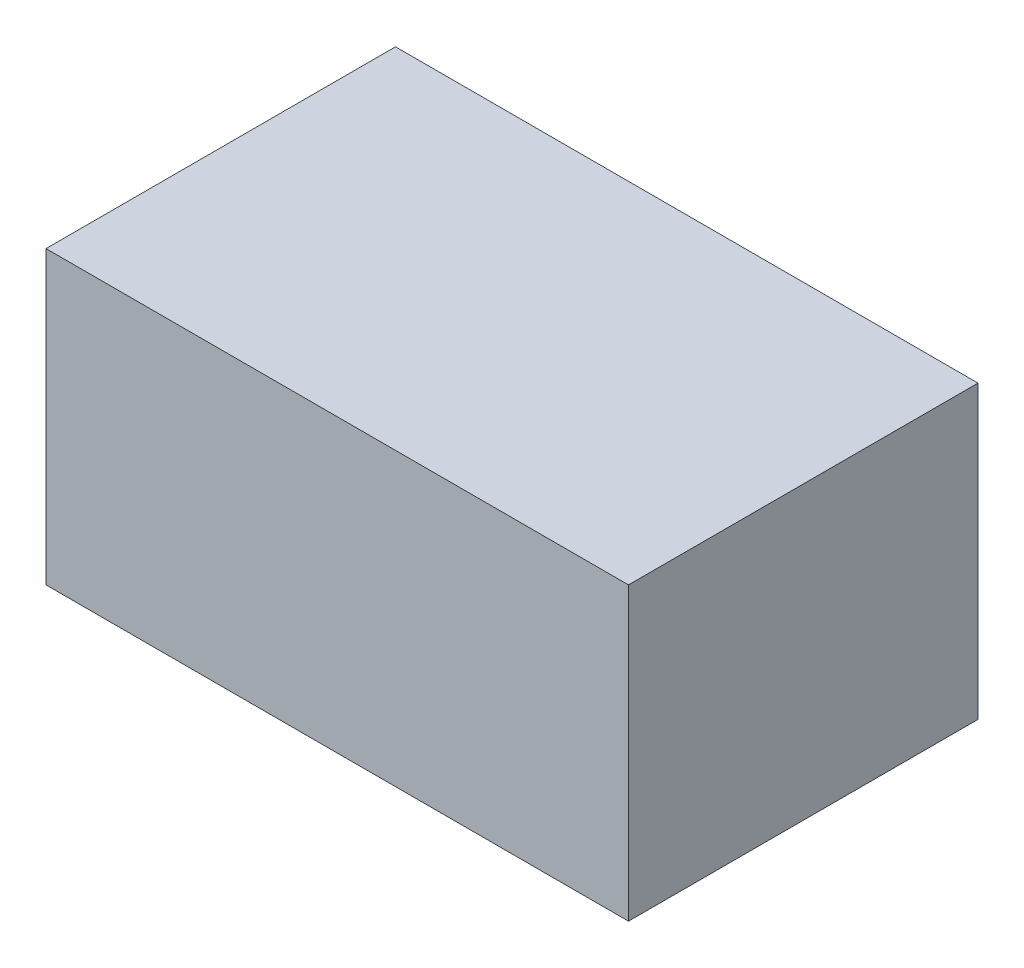
SolidWorks part; units mm, degrees
ref_plane "Front Plane" through (0, 0, 0) normal (0, 0, 1) x (1, 0, 0)
ref_plane "Top Plane" through (0, 0, 0) normal (0, 1, 0) x (1, 0, 0)
ref_plane "Right Plane" through (0, 0, 0) normal (1, 0, 0) x (0, 0, -1)
sketch "Sketch1" plane through (0, 0, 0) normal (0, 1, 0) x (1, 0, 0)
  line L1 (-100, 60) -> (100, 60)
  line L2 (-100, 60) -> (-100, -60)
  line L3 (-100, -60) -> (100, -60)
  line L4 (100, 60) -> (100, -60)
  line L5 (-100, 60) -> (100, -60) construction
  line L6 (-100, -60) -> (100, 60) construction
  point P0 (0, 0)
  dimension "D1" = 200
  dimension "D2" = 120
extrude "Boss-Extrude1" add sketch "Sketch1" along normal blind 50 and the other way blind 50 contours L1 L4 L3 L2
ref_axis "Axis3" through (0, 52.5, 0) along (0, -1, 0)
ref_axis "Axis4" through (0, 0, 66) along (0, 0, -1)
